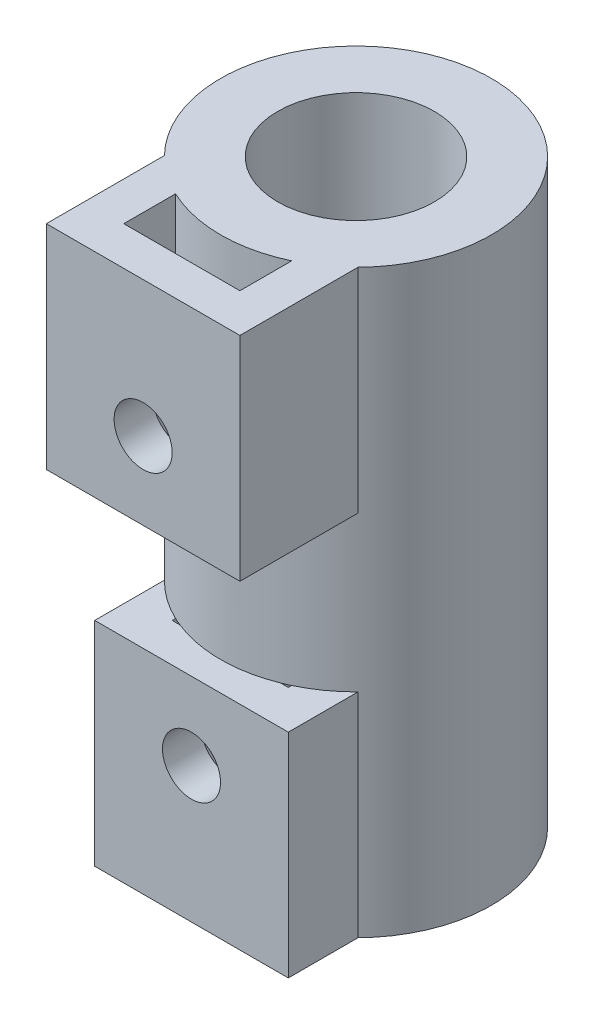
SolidWorks part; units mm, degrees
ref_plane "Front Plane" through (0, 0, 0) normal (0, 0, 1) x (1, 0, 0)
ref_plane "Top Plane" through (0, 0, 0) normal (0, 1, 0) x (1, 0, 0)
ref_plane "Right Plane" through (0, 0, 0) normal (1, 0, 0) x (0, 0, -1)
sketch "Sketch1" plane through (0, 0, 0) normal (0, 1, 0) x (1, 0, 0)
  circle A0 centre (0, 0) radius 7
  circle A1 centre (0, 0) radius 4.05
  circle A2 centre (0, 0) radius 1.7
  dimension "D1" = 8.1
  dimension "D2" = 14
  dimension "D3" = 3.4
extrude "Boss-Extrude1" add sketch "Sketch1" along normal blind 15 contours A0 A1 region at (-6.802, 0, 0)
extrude "Boss-Extrude2" add sketch "Sketch1<3>" against normal blind 15 contours A0 A1 | A1 A2 region at (-6.802, 0, 0) region at (-3.9354, 0, 0)
sketch "Sketch1<3>" plane through (0, 0, 0) normal (0, 1, 0) x (1, 0, 0) same geometry as "Sketch1"
sketch "Sketch3" plane through (0, -15, 0) normal (0, -1, 0) x (1, 0, 0)
  line L1 (-3, 6.5) -> (3, 6.5)
  line L2 (-3, 6.5) -> (-3, 3.5)
  line L3 (-3, 3.5) -> (3, 3.5)
  line L4 (3, 6.5) -> (3, 3.5)
  line L5 (-5, 3.5) -> (5, 3.5)
  line L6 (-5, 3.5) -> (-5, 8.5)
  line L7 (-5, 8.5) -> (5, 8.5)
  line L8 (5, 3.5) -> (5, 8.5)
  circle A0 centre (0, 0) radius 1.7 construction
  point P4 (0, 6.5)
  circle M9 centre (0, 0) radius 7
  dimension "D1" = 6
  dimension "D2" = 3
  dimension "D3" = 0
  dimension "D4" = 3.5
  dimension "D5" = 2
  dimension "D6" = 90
  dimension "D7" = 2
  dimension "D8" = 2
extrude "Cut-Extrude2" cut sketch "Sketch3" against normal blind 11 contours L4 L1 L2 L3 M9 region at (0, -15, 4.9945)
extrude "Boss-Extrude3" add sketch "Sketch3<3>" against normal blind 11 contours L8 L7 L6 L2 L1 L4 M9 region at (0, -15, 7.3408)
sketch "Sketch3<3>" plane through (0, -15, 0) normal (0, -1, 0) x (1, 0, 0) same geometry as "Sketch3"
sketch "Sketch4" plane through (0, 15, 0) normal (0, 1, 0) x (1, 0, 0)
  line L1 (-3, -6) -> (3, -6)
  line L2 (-3, -6) -> (-3, -9)
  line L3 (-3, -9) -> (3, -9)
  line L4 (3, -6) -> (3, -9)
  line L5 (5, -6) -> (-5, -6)
  line L6 (5, -6) -> (5, -11)
  line L7 (5, -11) -> (-5, -11)
  line L8 (-5, -6) -> (-5, -11)
  line L9 (-5, -6) -> (5, -6)
  line L10 (-5, -6) -> (-5, -4.899)
  line L11 (-5, -4.899) -> (5, -4.899)
  line L12 (5, -6) -> (5, -4.899)
  point P8 (0, -6)
  circle M10 centre (0, 0) radius 7
  dimension "D1" = 2
  dimension "D2" = 2
  dimension "D3" = 6
  dimension "D4" = 6
  dimension "D5" = 0
  dimension "D6" = 3
  dimension "D7" = 2
extrude "Boss-Extrude4" add sketch "Sketch4" against normal blind 11 contours L11 L5 L1 M10 | L5 L8 L7 L6 L4 L3 L2 M10 | L10 L5 M10 | L5 L12 M10 region at (0, 15, 5.4204) region at (0, 15, 9.0815) region at (-4.5561, 15, 5.6489) region at (4.5561, 15, 5.6489)
sketch "Sketch2" plane through (0, 0, 0) normal (0, 0, 1) x (1, 0, 0)
  line L0 (-7, -15) -> (7, -15) construction
  line L1 (4.05, 15) -> (-4.05, 15) construction
  circle A0 centre (0, 8) radius 1.5
  circle A1 centre (0, -8) radius 1.5
  dimension "D1" = 3
  dimension "D2" = 3
  dimension "D3" = 7
  dimension "D4" = 7
extrude "Cut-Extrude1" cut sketch "Sketch2" against normal through all both and the other way through all
